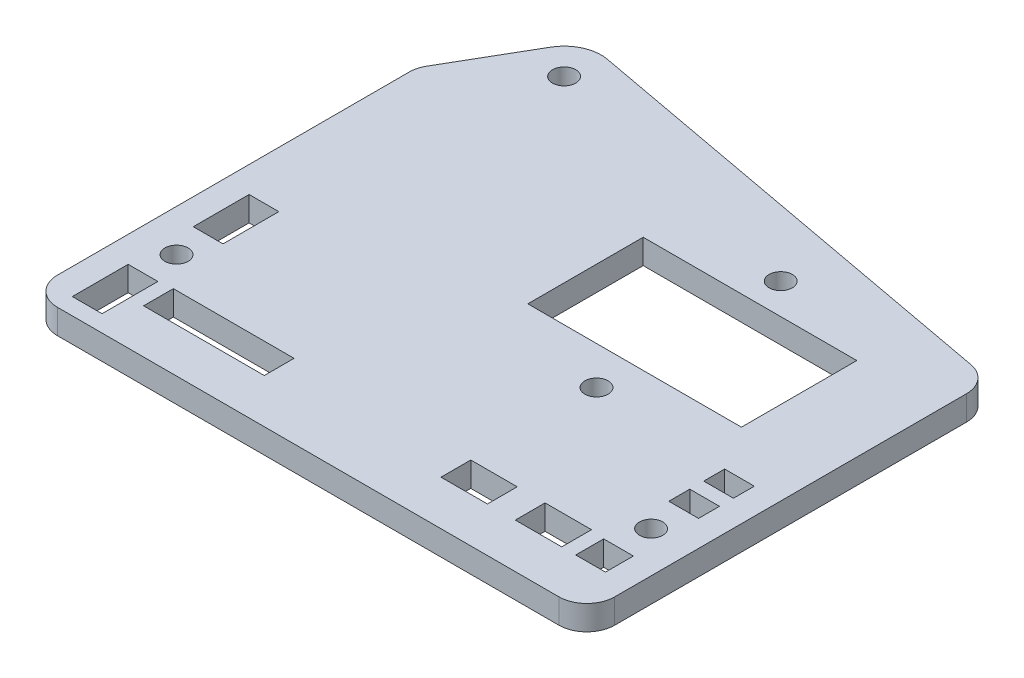
SolidWorks part; units mm, degrees
material "Acrylic (Medium-high impact)"
ref_plane "Front Plane" through (0, 0, 0) normal (0, 0, 1) x (1, 0, 0)
ref_plane "Top Plane" through (0, 0, 0) normal (0, 1, 0) x (1, 0, 0)
ref_plane "Right Plane" through (0, 0, 0) normal (1, 0, 0) x (0, 0, -1)
sketch "Sketch1" plane through (0, 0, 0) normal (0, 1, 0) x (1, 0, 0)
  line L0 (22.4482, -10.4787) -> (22.4482, -10.4849)
  line L1 (22.4482, -10.4849) -> (22.4482, -12.7319)
  line L2 (22.4482, -12.7319) -> (25.6427, -12.7319)
  line L3 (25.6427, -12.7319) -> (25.6427, -10.4787)
  line L4 (25.6427, -10.4787) -> (22.4482, -10.4787)
  line L5 (22.4482, -22.7324) -> (25.6427, -22.7324)
  line L6 (25.6427, -22.7324) -> (25.6427, -19.7322)
  line L7 (25.6427, -19.7322) -> (22.4482, -19.7322)
  line L8 (22.4482, -19.7322) -> (22.4482, -22.7324)
  line L9 (-25.4666, -12.7319) -> (-25.4666, -6.7316)
  line L10 (-25.4666, -6.7316) -> (-28.661, -6.7316)
  line L11 (-28.661, -6.7316) -> (-28.661, -12.7319)
  line L12 (-28.661, -12.7319) -> (-25.4666, -12.7319)
  line L13 (-25.4666, -25.7324) -> (-25.4666, -19.7322)
  line L14 (-25.4666, -19.7322) -> (-28.661, -19.7322)
  line L15 (-28.661, -19.7322) -> (-28.661, -25.7324)
  line L16 (-28.661, -25.7324) -> (-25.4666, -25.7324)
  line L17 (15.951, -22.7324) -> (15.951, -19.5323)
  line L18 (15.951, -19.5323) -> (20.942, -19.5323)
  line L19 (20.942, -19.5323) -> (20.942, -22.7324)
  line L20 (20.942, -22.7324) -> (15.951, -22.7324)
  line L21 (12.9563, -22.7324) -> (7.9651, -22.7324)
  line L22 (7.9651, -22.7324) -> (7.9651, -19.5323)
  line L23 (7.9651, -19.5323) -> (12.9563, -19.5323)
  line L24 (12.9563, -19.5323) -> (12.9563, -22.7324)
  line L25 (25.4429, -27.5324) -> (-28.4561, -27.5324)
  line L26 (-31.456, -24.5325) -> (-31.456, 13.2693)
  line L27 (-31.0509, 14.776) -> (-26.1748, 23.1862)
  line L28 (-21.9978, 25.1075) -> (25.9832, 16.22)
  line L29 (28.4378, 13.269) -> (28.4376, -24.5377)
  line L30 (-10.9933, -19.5326) -> (-10.9933, -19.5668)
  line L31 (-10.9933, -19.5668) -> (-23.9701, -19.5668)
  line L32 (-23.9701, -19.5668) -> (-23.9701, -22.767)
  line L33 (-23.9701, -22.767) -> (-10.9933, -22.767)
  line L34 (-10.9933, -22.767) -> (-10.9933, -19.5326)
  line L35 (19.4537, -1.9316) -> (-3.5057, -1.9316)
  line L36 (-3.5057, -1.9316) -> (-3.5057, 10.469)
  line L37 (-3.5057, 10.469) -> (19.4537, 10.469)
  line L38 (19.4537, 10.469) -> (19.4537, -1.9316)
  line L39 (25.6427, -6.7255) -> (25.6427, -6.7316)
  line L40 (25.6427, -6.7316) -> (22.4482, -6.7316)
  line L41 (22.4482, -6.7316) -> (22.4482, -8.9787)
  line L42 (22.4482, -8.9787) -> (25.6427, -8.9787)
  line L43 (25.6427, -8.9787) -> (25.6427, -6.7255)
  arc A0 (-31.456, -24.5325) -> (-28.4561, -27.5324) centre (-28.4561, -24.5325) ccw
  arc A1 (25.4429, -27.5324) -> (28.4376, -24.5377) centre (25.4429, -24.5377) ccw
  arc A2 (28.4378, 13.269) -> (25.9832, 16.22) centre (25.4366, 13.269) ccw
  arc A3 (-21.9978, 25.1075) -> (-26.1748, 23.1862) centre (-22.7242, 21.1856) ccw
  arc A4 (-31.0509, 14.776) -> (-31.456, 13.2693) centre (-28.4522, 13.2693) ccw
  circle A5 centre (-22.7242, 21.1856) radius 1.25
  circle A6 centre (-26.964, -16.2321) radius 1.25
  circle A7 centre (7.974, 13.769) radius 1.25
  circle A8 centre (7.974, -6.0315) radius 1.25
  circle A9 centre (24.0455, -16.2321) radius 1.25
  point P5 (-26.964, -16.2321)
  point P7 (7.974, -6.0315)
  point P8 (24.0455, -16.2321)
  point P9 (7.974, 13.769)
  dimension "D1" = 2.5
  dimension "D2" = 2.5
extrude "Boss-Extrude1" add sketch "Sketch1" along normal blind 2.6461 contours L27 A4 L26 A0 L25 A1 L29 A2 L28 A3 A9 A8 A7 A6 A5 L37 L38 L35 L36 L23 L24 L21 L22 L19 L20 L17 L18 L4 L3 L2 L1 L0 L8 L7 L6 L5 L12 L11 L10 L9 region at (-3.2783, 0, 3.4432)
